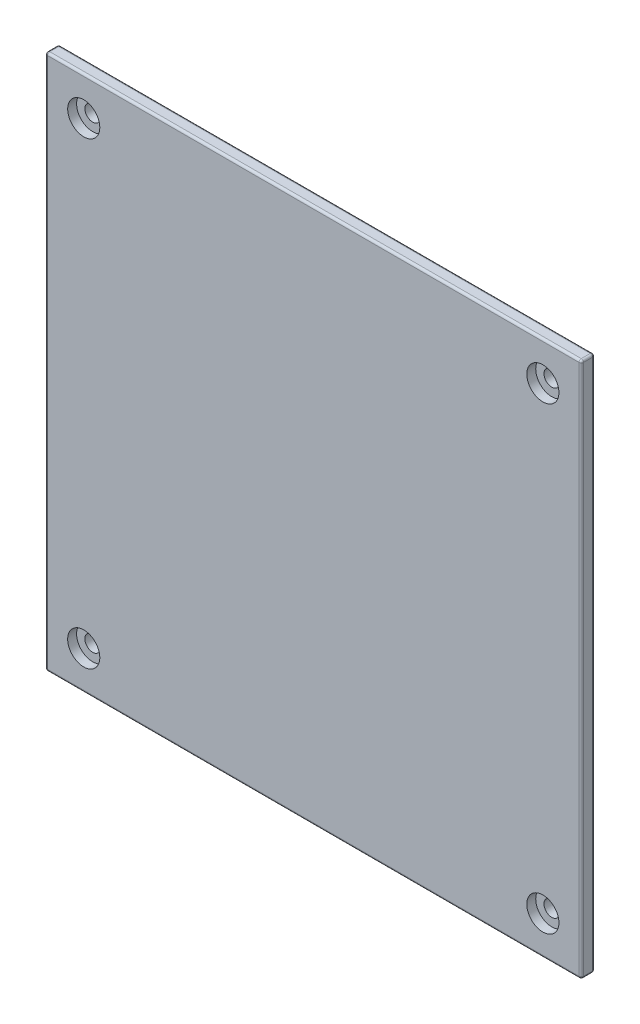
SolidWorks part; units mm, degrees
material "PVC 0.007 Plasticizado"
ref_plane "Plano frontal" through (0, 0, 0) normal (0, 0, 1) x (1, 0, 0)
ref_plane "Plano superior" through (0, 0, 0) normal (0, 1, 0) x (1, 0, 0)
ref_plane "Plano direito" through (0, 0, 0) normal (1, 0, 0) x (0, 0, -1)
sketch "Esboço1" plane through (0, 0, 0) normal (0, 0, 1) x (1, 0, 0)
  line L1 (-60, -60) -> (60, -60)
  line L2 (-60, -60) -> (-60, 60)
  line L3 (-60, 60) -> (60, 60)
  line L4 (60, -60) -> (60, 60)
  line L5 (-60, -60) -> (60, 60) construction
  line L6 (-60, 60) -> (60, -60) construction
  point P0 (0, 0)
  dimension "D1" = 120
  dimension "D2" = 120
extrude "Ressalto-extrusão1" add sketch "Esboço1" along normal blind 3
sketch "Esboço2" plane through (0, 0, 0) normal (0, 0, -1) x (-1, 0, 0)
  line L8 (-56.4, 56.4) -> (-56.4, -56.4)
  line L9 (-56.4, -56.4) -> (56.4, -56.4)
  line L10 (56.4, -56.4) -> (56.4, 56.4)
  line L11 (56.4, 56.4) -> (-56.4, 56.4)
  line L12 (-56.4, 56.4) -> (-56.4, -56.4)
  line L13 (-56.4, -56.4) -> (56.4, -56.4)
  line L14 (56.4, -56.4) -> (56.4, 56.4)
  line L15 (56.4, 56.4) -> (-56.4, 56.4)
  dimension "D1" = 3.6
extrude "Ressalto-extrusão2" add sketch "Esboço2" along normal blind 2
sketch "Esboço3" plane through (0, 0, -2) normal (0, 0, -1) x (-1, 0, 0)
  line L8 (54.4, 54.4) -> (-54.4, 54.4)
  line L9 (-54.4, 54.4) -> (-54.4, -54.4)
  line L10 (-54.4, -54.4) -> (54.4, -54.4)
  line L11 (54.4, -54.4) -> (54.4, 54.4)
  line L12 (54.4, 54.4) -> (-54.4, 54.4)
  line L13 (-54.4, 54.4) -> (-54.4, -54.4)
  line L14 (-54.4, -54.4) -> (54.4, -54.4)
  line L15 (54.4, -54.4) -> (54.4, 54.4)
  dimension "D1" = 2
extrude "Corte-extrusão1" cut sketch "Esboço3" against normal blind 2
sketch "Esboço5" plane through (0, 0, 0) normal (0, 0, -1) x (-1, 0, 0)
  line L0 (56.4, -56.4) -> (56.4, 56.4) construction
  line L1 (56.4, 56.4) -> (-56.4, 56.4) construction
  line L2 (60, 60) -> (60, -60) construction
  circle A0 centre (51.4, 51.4) radius 5
  dimension "D1" = 8.6
extrude "Ressalto-extrusão3" add sketch "Esboço5" along normal blind 2
mirror "Espelhar1" about plane through (0, 0, 0) normal (1, 0, 0) of "Ressalto-extrusão3"
mirror "Espelhar2" about plane through (0, 0, 0) normal (0, 1, 0) of "Espelhar1"
chamfer "Chanfro1" distance 0.5 angle 45 4 edges at (-56.4, 0, -2) (0, -56.4, -2) (56.4, 0, -2) (0, 56.4, -2)
fillet "Filete1" radius 2 8 edges at (0, -54.4, 0) (47.8645, -47.8645, 0) (54.4, 0, 0) (47.8645, 47.8645, 0) (0, 54.4, 0) (-47.8645, 47.8645, 0) (-54.4, 0, 0) (-47.8645, -47.8645, 0)
sketch "Esboço6" plane through (0, 0, 3) normal (0, 0, 1) x (1, 0, 0)
  line L0 (-60, 60) -> (-60, -60) construction
  line L1 (60, 60) -> (-60, 60) construction
  circle A0 centre (-51.4, 51.4) radius 3.6
  dimension "D1" = 8.6
  dimension "D3" = 7.2
  dimension "D2" = 8.6
extrude "Corte-extrusão2" cut sketch "Esboço6" against normal blind 2
sketch "Esboço7" plane through (0, 0, 1) normal (0, 0, 1) x (1, 0, 0)
  circle A0 centre (-51.4, 51.4) radius 1.75
  dimension "D1" = 3.5
extrude "Corte-extrusão3" cut sketch "Esboço7" against normal through all
mirror "Espelhar3" about plane through (0, 0, 0) normal (1, 0, 0) of "Corte-extrusão2", "Corte-extrusão3"
mirror "Espelhar4" about plane through (0, 0, 0) normal (0, 1, 0) of "Espelhar3"
fillet "Filete2" radius 0.5 12 edges at (0, -60, 3) (0, -60, 0) (60, -60, 1.5) (60, 0, 3) (60, 0, 0) (-60, 0, 3) (-60, -60, 1.5) (-60, 0, 0) (60, 60, 1.5) (0, 60, 3) (-60, 60, 1.5) (0, 60, 0)
